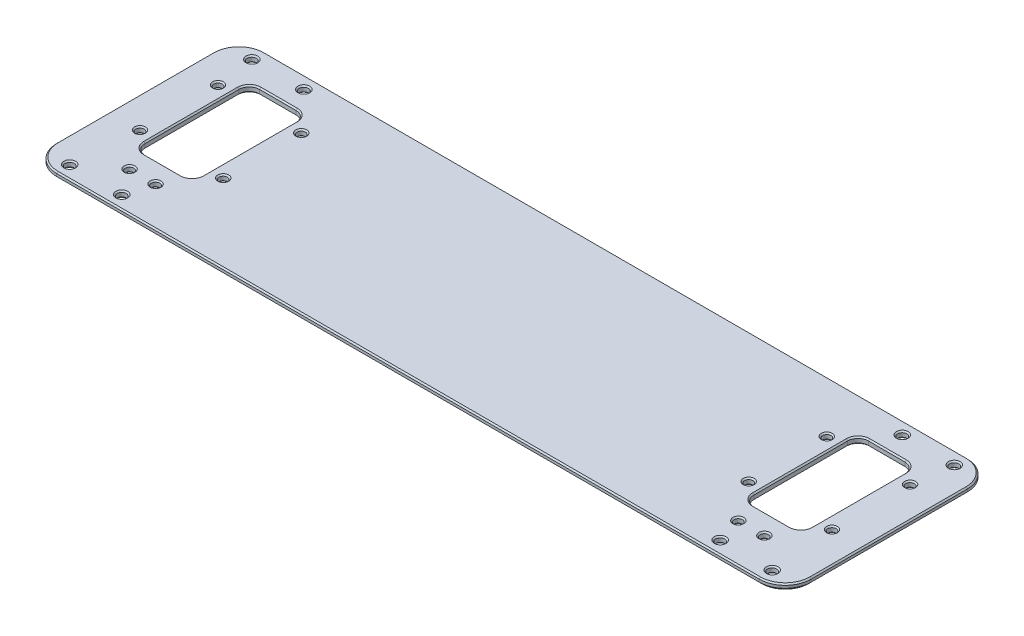
SolidWorks part; units mm, degrees
ref_plane "Front Plane" through (0, 0, 0) normal (0, 0, 1) x (1, 0, 0)
ref_plane "Top Plane" through (0, 0, 0) normal (0, 1, 0) x (1, 0, 0)
ref_plane "Right Plane" through (0, 0, 0) normal (1, 0, 0) x (0, 0, -1)
sketch "Sketch1" plane through (0, 0, 0) normal (0, 1, 0) x (1, 0, 0)
  line L0 (128.27, 0) -> (-128.27, 0) construction
  line L1 (184.15, 50.8) -> (-184.15, 50.8)
  line L2 (184.15, 50.8) -> (184.15, -50.8)
  line L3 (184.15, -50.8) -> (-184.15, -50.8)
  line L4 (-184.15, 50.8) -> (-184.15, -50.8)
  line L5 (184.15, 50.8) -> (-184.15, -50.8) construction
  line L6 (184.15, -50.8) -> (-184.15, 50.8) construction
  line L7 (-128.27, 0) -> (-128.27, 25.4) construction
  line L8 (-128.27, 25.4) -> (-134.62, 25.4) construction
  line L9 (-128.27, -12.7) -> (-134.62, -12.7) construction
  line L12 (-162.56, -21.59) -> (-162.56, 34.29)
  line L15 (-134.62, -21.59) -> (-162.56, -21.59)
  line L17 (-134.62, 34.29) -> (-162.56, 34.29)
  line L18 (0, 50.8) -> (0, -50.8) construction
  line L19 (-134.62, 34.29) -> (-134.62, -21.59)
  line L20 (-162.56, 25.4) -> (-168.91, 25.4) construction
  line L21 (128.27, 25.4) -> (134.62, 25.4) construction
  line L22 (162.56, 25.4) -> (168.91, 25.4) construction
  line L23 (-162.56, -12.7) -> (-168.91, -12.7) construction
  line L24 (134.62, 34.29) -> (162.56, 34.29)
  line L25 (128.27, 25.4) -> (128.27, -12.7) construction
  line L26 (128.27, -12.7) -> (134.62, -12.7) construction
  line L27 (134.62, 34.29) -> (134.62, -21.59)
  line L28 (134.62, -21.59) -> (162.56, -21.59)
  line L29 (162.56, -21.59) -> (162.56, 34.29)
  line L30 (162.56, -12.7) -> (168.91, -12.7) construction
  line L31 (184.15, -31.75) -> (154.94, -31.75) construction
  line L32 (146.05, 44.45) -> (184.15, 44.45) construction
  line L33 (154.94, -31.75) -> (142.24, -31.75) construction
  line L34 (146.05, -44.45) -> (184.15, -44.45) construction
  line L35 (-146.05, -44.45) -> (-184.15, -44.45) construction
  line L36 (-146.05, 44.45) -> (-184.15, 44.45) construction
  line L37 (-128.27, 0) -> (-128.27, -12.7) construction
  line L38 (-184.15, -31.75) -> (-154.94, -31.75) construction
  line L39 (-154.94, -31.75) -> (-142.24, -31.75) construction
  circle A0 centre (-128.27, 25.4) radius 2.032
  circle A1 centre (-128.27, -12.7) radius 2.032
  circle A2 centre (-168.91, 25.4) radius 2.032
  circle A3 centre (-168.91, -12.7) radius 2.032
  circle A4 centre (168.91, 25.4) radius 2.032
  circle A5 centre (128.27, 25.4) radius 2.032
  circle A6 centre (128.27, -12.7) radius 2.032
  circle A7 centre (168.91, -12.7) radius 2.032
  circle A8 centre (171.45, -44.45) radius 2.2225
  circle A9 centre (146.05, -44.45) radius 2.2225
  circle A10 centre (171.45, 44.45) radius 2.2225
  circle A11 centre (146.05, 44.45) radius 2.2225
  circle A12 centre (-146.05, -44.45) radius 2.2225
  circle A13 centre (-171.45, -44.45) radius 2.2225
  circle A14 centre (-146.05, 44.45) radius 2.2225
  circle A15 centre (-171.45, 44.45) radius 2.2225
  circle A16 centre (142.24, -31.75) radius 2.032
  circle A17 centre (154.94, -31.75) radius 2.032
  circle A18 centre (-154.94, -31.75) radius 2.032
  circle A19 centre (-142.24, -31.75) radius 2.032
  point P0 (0, 0)
  point P11 (-128.27, 0)
  point P13 (-134.62, 25.4)
  point P17 (-134.62, -12.7)
  point P37 (0, 0)
  point P50 (171.45, 44.45)
  point P51 (146.05, 44.45)
  point P56 (171.45, -44.45)
  point P57 (146.05, -44.45)
  point P82 (0, 0)
  point P83 (0, 0)
  dimension "D5" = 4.064
  dimension "D6" = 8.89
  dimension "D18" = 4.445
  dimension "D1" = 368.3
  dimension "D2" = 101.6
  dimension "D3" = 128.27
  dimension "D4" = 38.1
  dimension "D7" = 6.35
  dimension "D8" = 27.94
  dimension "D9" = 55.88
  dimension "D10" = 8.89
  dimension "D11" = 8.89
  dimension "D12" = 8.89
  dimension "D13" = 15.24
  dimension "D14" = 12.7
  dimension "D15" = 38.1
  dimension "D16" = 12.7
  dimension "D17" = 38.1
  dimension "D19" = 25.4
  dimension "D20" = 6.35
  dimension "D21" = 6.35
  dimension "D22" = 19.05
  dimension "D23" = 29.21
  dimension "D24" = 12.7
  dimension "D25" = 7.62
  dimension "D26" = 7.62
extrude "Boss-Extrude1" add sketch "Sketch1" along normal blind 3.175
fillet "Fillet1" radius 5.08 4 edges at (-134.62, 1.5875, 21.59) (-162.56, 1.5875, 21.59) (-162.56, 1.5875, -34.29) (-134.62, 1.5875, -34.29)
fillet "Fillet2" radius 5.08 4 edges at (162.56, 1.5875, 21.59) (134.62, 1.5875, 21.59) (134.62, 1.5875, -34.29) (162.56, 1.5875, -34.29)
fillet "Fillet3" radius 12.7 4 edges at (184.15, 1.5875, 50.8) (184.15, 1.5875, -50.8) (-184.15, 1.5875, 50.8) (-184.15, 1.5875, -50.8)
chamfer "Chamfer3" distance 0.635 angle 45 32 edges at (161.0721, 3.175, -32.8021) (148.59, 3.175, -34.29) (136.1079, 3.175, -32.8021) (162.56, 3.175, -6.35) (161.0721, 3.175, 20.1021) (148.59, 3.175, 21.59) (136.1079, 3.175, 20.1021) (134.62, 3.175, -6.35) (136.1079, 0, -32.8021) (148.59, 0, -34.29) (161.0721, 0, -32.8021) (162.56, 0, -6.35) (161.0721, 0, 20.1021) (148.59, 0, 21.59) (136.1079, 0, 20.1021) (134.62, 0, -6.35) (-136.1079, 3.175, 20.1021) (-148.59, 3.175, 21.59) (-134.62, 3.175, -6.35) (-136.1079, 3.175, -32.8021) (-148.59, 3.175, -34.29) (-161.0721, 3.175, 20.1021) (-161.0721, 3.175, -32.8021) (-162.56, 3.175, -6.35) (-136.1079, 0, 20.1021) (-148.59, 0, 21.59) (-134.62, 0, -6.35) (-136.1079, 0, -32.8021) (-148.59, 0, -34.29) (-161.0721, 0, 20.1021) (-162.56, 0, -6.35) (-161.0721, 0, -32.8021)
chamfer "Chamfer4" distance 1.27 angle 45 8 edges at (180.4303, 0, -47.0803) (0, 0, -50.8) (-180.4303, 0, -47.0803) (-184.15, 0, 0) (-180.4303, 0, 47.0803) (0, 0, 50.8) (180.4303, 0, 47.0803) (184.15, 0, 0)
chamfer "Chamfer5" distance 0.635 angle 45 16 edges at (-168.91, 0, 14.732) (-168.91, 0, -23.368) (-128.27, 0, -23.368) (-128.27, 0, 14.732) (168.91, 0, 10.668) (168.91, 0, -27.432) (128.27, 0, 10.668) (128.27, 0, -27.432) (-171.45, 0, -46.6725) (-146.05, 0, -46.6725) (-146.05, 0, 42.2275) (-171.45, 0, 42.2275) (146.05, 0, 46.6725) (171.45, 0, 46.6725) (146.05, 0, -42.2275) (171.45, 0, -42.2275)
chamfer "Chamfer6" distance 0.635 angle 45 8 edges at (180.4303, 3.175, 47.0803) (184.15, 3.175, 0) (180.4303, 3.175, -47.0803) (0, 3.175, 50.8) (-180.4303, 3.175, 47.0803) (-184.15, 3.175, 0) (0, 3.175, -50.8) (-180.4303, 3.175, -47.0803)
chamfer "Chamfer7" distance 0.635 angle 45 16 edges at (-168.91, 3.175, 14.732) (-168.91, 3.175, -23.368) (-128.27, 3.175, -23.368) (-128.27, 3.175, 14.732) (128.27, 3.175, 10.668) (128.27, 3.175, -27.432) (168.91, 3.175, -27.432) (168.91, 3.175, 10.668) (146.05, 3.175, -42.2275) (171.45, 3.175, -42.2275) (146.05, 3.175, 46.6725) (171.45, 3.175, 46.6725) (-146.05, 3.175, -46.6725) (-171.45, 3.175, -46.6725) (-171.45, 3.175, 42.2275) (-146.05, 3.175, 42.2275)
chamfer "Chamfer8" distance 0.635 angle 45 8 edges at (-154.94, 0, 29.718) (-142.24, 0, 29.718) (154.94, 0, 33.782) (142.24, 0, 33.782) (154.94, 3.175, 33.782) (142.24, 3.175, 33.782) (-154.94, 3.175, 29.718) (-142.24, 3.175, 29.718)
